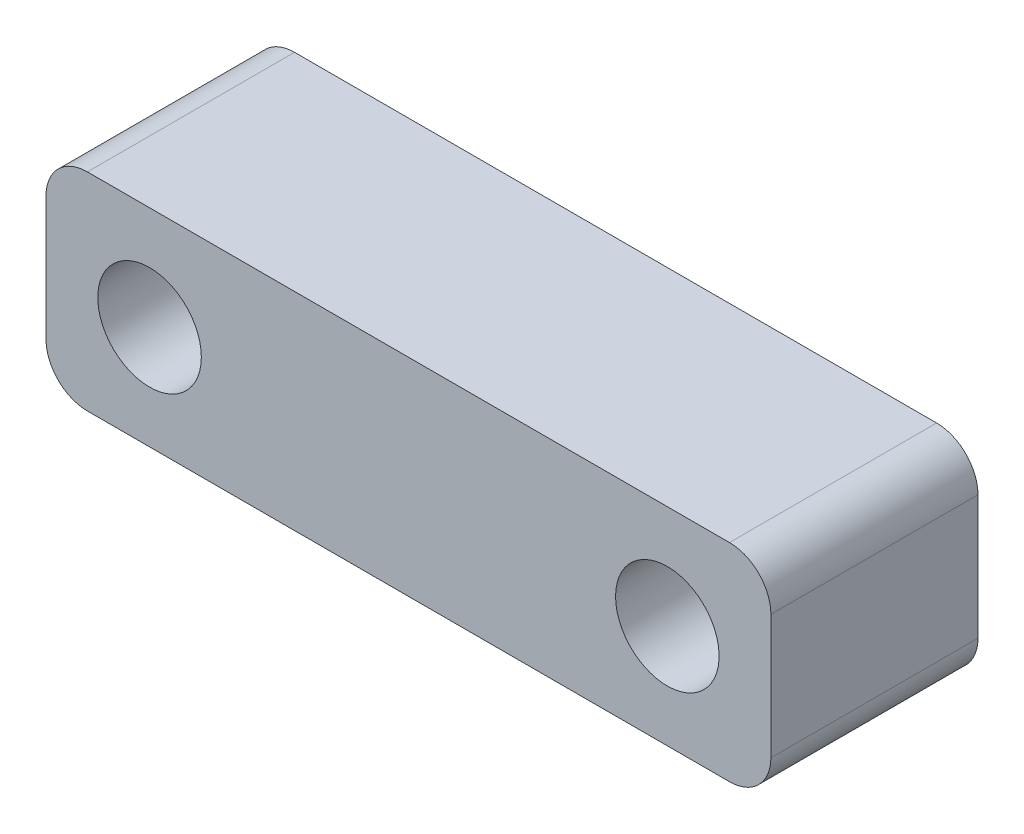
SolidWorks part; units mm, degrees
ref_plane "Plan de face" through (0, 0, 0) normal (0, 0, 1) x (1, 0, 0)
ref_plane "Plan de dessus" through (0, 0, 0) normal (0, 1, 0) x (1, 0, 0)
ref_plane "Plan de droite" through (0, 0, 0) normal (1, 0, 0) x (0, 0, -1)
sketch "Esquisse1" plane through (0, 0, 0) normal (0, 0, 1) x (1, 0, 0)
  line L0 (-16.3416, 3.3696) -> (18.6584, 3.3696) construction
  line L1 (-16.3416, 8.3696) -> (18.6584, 8.3696)
  line L2 (-16.3416, 8.3696) -> (-16.3416, -1.6304)
  line L3 (-16.3416, -1.6304) -> (18.6584, -1.6304)
  line L4 (18.6584, 8.3696) -> (18.6584, -1.6304)
  line L5 (-16.3416, 3.3696) -> (-11.3416, 3.3696) construction
  line L6 (1.1584, 8.3696) -> (1.1584, -1.6304) construction
  circle A0 centre (-11.3416, 3.3696) radius 2.5
  circle A1 centre (13.6584, 3.3696) radius 2.5
  point P12 (0, 0)
  dimension "D1" = 35
  dimension "D2" = 10
  dimension "D3" = 5
extrude "Boss.-Extru.1" add sketch "Esquisse1" along normal blind 10
fillet "Congé1" radius 2 1 edges at (-16.3416, 8.3696, 5)
fillet "Congé2" radius 2 1 edges at (-16.3416, -1.6304, 5)
fillet "Congé3" radius 2 1 edges at (18.6584, 8.3696, 5)
fillet "Congé4" radius 2 1 edges at (18.6584, -1.6304, 5)
